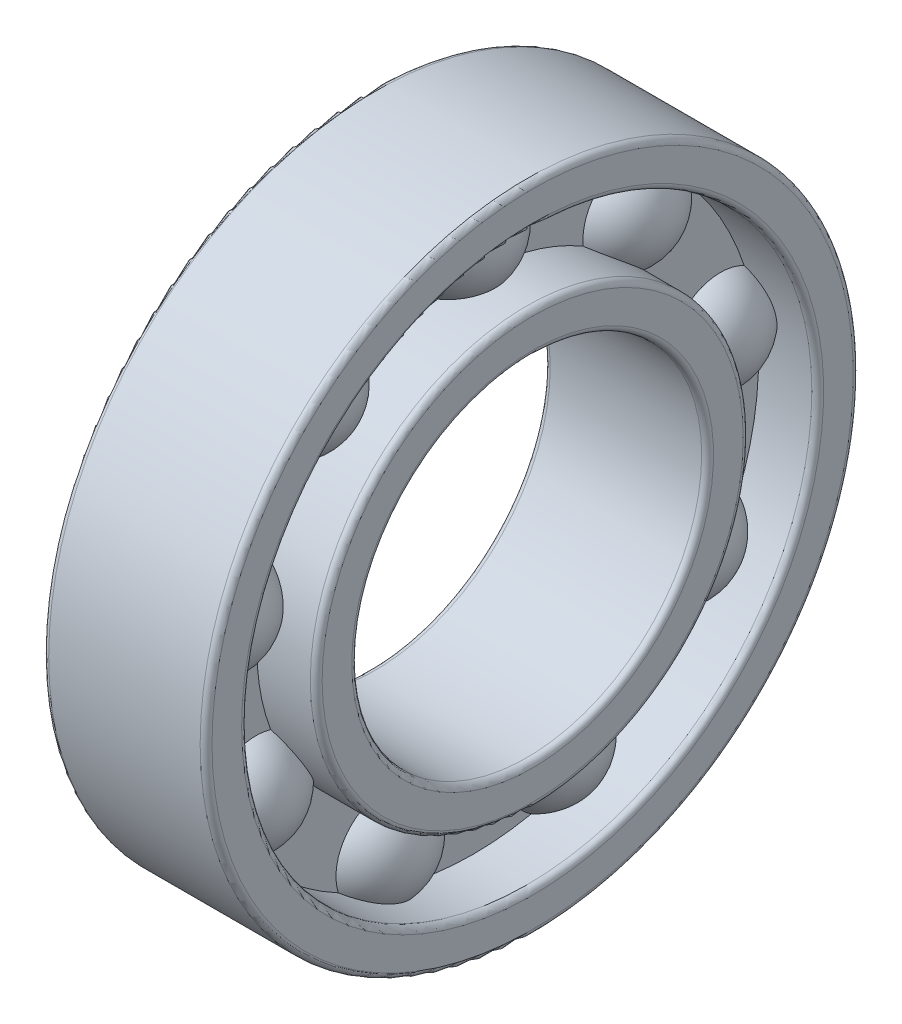
SolidWorks part; units mm, degrees
ref_plane "Front" through (0, 0, 0) normal (0, 0, 1) x (1, 0, 0)
ref_plane "Top" through (0, 0, 0) normal (0, 1, 0) x (1, 0, 0)
ref_plane "Right" through (0, 0, 0) normal (1, 0, 0) x (0, 0, -1)
sketch "Sketch1" plane through (0, 0, 0) normal (0, 0, 1) x (1, 0, 0)
  line L0 (-0.96, 10.75) -> (0.96, 10.75) construction
  line L1 (-3.246, 7.5) -> (3.246, 7.5)
  line L2 (-3.5, 7.754) -> (-3.5, 9.024)
  line L3 (-3.246, 14) -> (3.246, 14)
  line L4 (3.5, 7.754) -> (3.5, 9.024)
  line L5 (3.246, 12.222) -> (0.96, 12.222)
  line L6 (3.5, 12.476) -> (3.5, 13.746)
  line L7 (3.246, 9.278) -> (0.96, 9.278)
  line L8 (0.96, 12.222) -> (0.96, 9.278)
  line L9 (-3.246, 12.222) -> (-0.96, 12.222)
  line L10 (-3.5, 12.476) -> (-3.5, 13.746)
  line L11 (-3.246, 9.278) -> (-0.96, 9.278)
  line L12 (-0.96, 12.222) -> (-0.96, 9.278)
  circle A0 centre (0, 10.75) radius 2.413 construction
  arc A1 (3.246, 7.5) -> (3.5, 7.754) centre (3.246, 7.754) ccw
  arc A2 (-3.246, 7.5) -> (-3.5, 7.754) centre (-3.246, 7.754) cw
  arc A3 (-3.246, 9.278) -> (-3.5, 9.024) centre (-3.246, 9.024) ccw
  arc A4 (-3.246, 12.222) -> (-3.5, 12.476) centre (-3.246, 12.476) cw
  arc A5 (-3.5, 13.746) -> (-3.246, 14) centre (-3.246, 13.746) cw
  arc A6 (3.246, 14) -> (3.5, 13.746) centre (3.246, 13.746) cw
  arc A7 (3.246, 12.222) -> (3.5, 12.476) centre (3.246, 12.476) ccw
  arc A8 (3.246, 9.278) -> (3.5, 9.024) centre (3.246, 9.024) cw
  point P25 (-3.5, 12.222)
  point P32 (3.5, 12.222)
  dimension "D9" = 0.254
  dimension "D10" = 4.826
  dimension "D1" = 7.5
  dimension "D2" = 14
  dimension "D3" = 7
  dimension "D4" = 3.5
  dimension "D5" = 1.778
  dimension "D6" = 1.778
  dimension "D7" = 2.54
  dimension "D8" = 2.54
sketch "Sketch2" plane through (0, 0, 0) normal (0, 0, 1) x (1, 0, 0)
  line L0 (-3.0494, 0) -> (3.0494, 0) construction
  line L12 (3.246, 14) -> (-3.246, 14)
  line L13 (3.5, 12.476) -> (3.5, 13.746)
  line L14 (0.96, 12.222) -> (3.246, 12.222)
  line L15 (0.96, 9.278) -> (0.96, 12.222)
  line L16 (3.246, 9.278) -> (0.96, 9.278)
  line L17 (3.5, 7.754) -> (3.5, 9.024)
  line L18 (-3.246, 7.5) -> (3.246, 7.5)
  line L19 (-3.5, 9.024) -> (-3.5, 7.754)
  line L20 (-0.96, 9.278) -> (-3.246, 9.278)
  line L21 (-0.96, 12.222) -> (-0.96, 9.278)
  line L22 (-3.246, 12.222) -> (-0.96, 12.222)
  line L23 (-3.5, 13.746) -> (-3.5, 12.476)
  line L24 (3.246, 14) -> (-3.246, 14)
  line L25 (3.5, 12.476) -> (3.5, 13.746)
  line L26 (0.96, 12.222) -> (3.246, 12.222)
  line L27 (0.96, 9.278) -> (0.96, 12.222)
  line L28 (3.246, 9.278) -> (0.96, 9.278)
  line L29 (3.5, 7.754) -> (3.5, 9.024)
  line L30 (-3.246, 7.5) -> (3.246, 7.5)
  line L31 (-3.5, 9.024) -> (-3.5, 7.754)
  line L32 (-0.96, 9.278) -> (-3.246, 9.278)
  line L33 (-0.96, 12.222) -> (-0.96, 9.278)
  line L34 (-3.246, 12.222) -> (-0.96, 12.222)
  line L35 (-3.5, 13.746) -> (-3.5, 12.476)
  arc A8 (3.5, 13.746) -> (3.246, 14) centre (3.246, 13.746) ccw
  arc A9 (3.246, 12.222) -> (3.5, 12.476) centre (3.246, 12.476) ccw
  arc A10 (3.5, 9.024) -> (3.246, 9.278) centre (3.246, 9.024) ccw
  arc A11 (3.246, 7.5) -> (3.5, 7.754) centre (3.246, 7.754) ccw
  arc A12 (-3.5, 7.754) -> (-3.246, 7.5) centre (-3.246, 7.754) ccw
  arc A13 (-3.246, 9.278) -> (-3.5, 9.024) centre (-3.246, 9.024) ccw
  arc A14 (-3.5, 12.476) -> (-3.246, 12.222) centre (-3.246, 12.476) ccw
  arc A15 (-3.246, 14) -> (-3.5, 13.746) centre (-3.246, 13.746) ccw
  arc A16 (3.5, 13.746) -> (3.246, 14) centre (3.246, 13.746) ccw
  arc A17 (3.246, 12.222) -> (3.5, 12.476) centre (3.246, 12.476) ccw
  arc A18 (3.5, 9.024) -> (3.246, 9.278) centre (3.246, 9.024) ccw
  arc A19 (3.246, 7.5) -> (3.5, 7.754) centre (3.246, 7.754) ccw
  arc A20 (-3.5, 7.754) -> (-3.246, 7.5) centre (-3.246, 7.754) ccw
  arc A21 (-3.246, 9.278) -> (-3.5, 9.024) centre (-3.246, 9.024) ccw
  arc A22 (-3.5, 12.476) -> (-3.246, 12.222) centre (-3.246, 12.476) ccw
  arc A23 (-3.246, 14) -> (-3.5, 13.746) centre (-3.246, 13.746) ccw
  dimension "D1" = 0
revolve "Revolve1" add sketch "Sketch2" angle 360 about L0
sketch "Sketch3" plane through (0, 0, 0) normal (0, 0, 1) x (1, 0, 0)
  line L0 (0, 13.163) -> (0, 8.337)
  line L1 (0, 8.337) -> (0, 11.2025) construction
  circle A0 centre (0, 10.75) radius 2.413 construction
  arc A1 (0, 8.337) -> (0, 13.163) centre (0, 10.75) ccw
revolve "Revolve2" add sketch "Sketch3" angle 360 about L1
ref_axis "Axis1" through (3.246, 0, 0) along (-1, 0, 0)
pattern_circular "CirPattern1" count 9 over 360 about axis through (3.246, 0, 0) along (-1, 0, 0) of "Revolve2"
